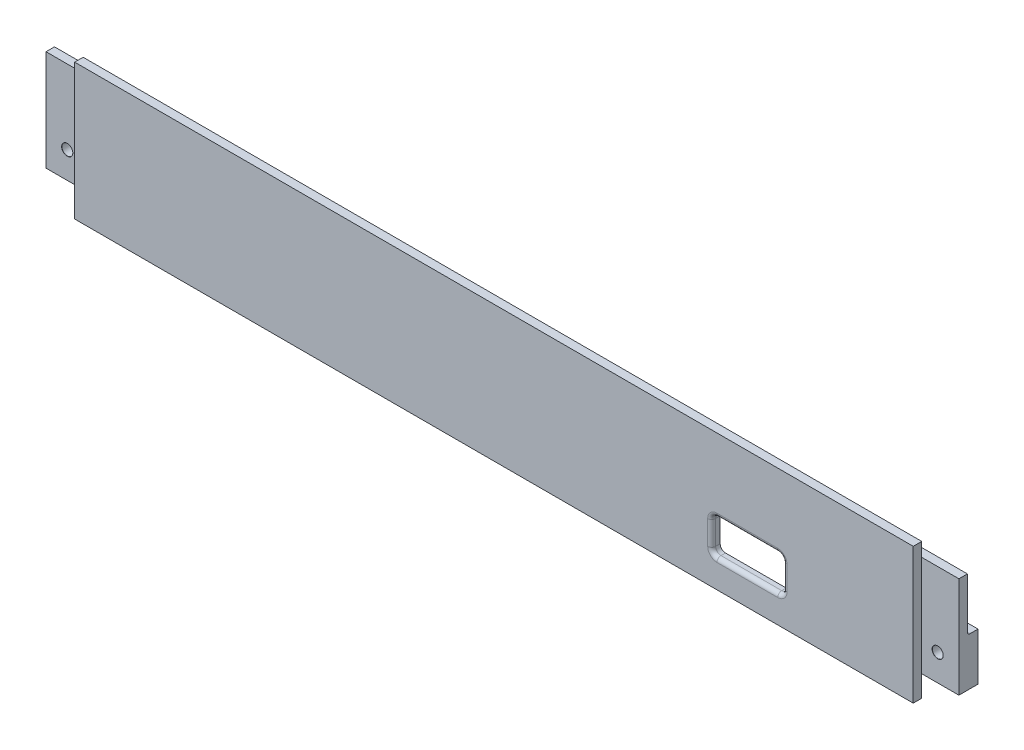
SolidWorks part; units mm, degrees
ref_plane "Front Plane" through (0, 0, 0) normal (0, 0, 1) x (1, 0, 0)
ref_plane "Top Plane" through (0, 0, 0) normal (0, 1, 0) x (1, 0, 0)
ref_plane "Right Plane" through (0, 0, 0) normal (1, 0, 0) x (0, 0, -1)
sketch "Sketch1" plane through (0, 0, 0) normal (0, 0, 1) x (1, 0, 0)
  line L0 (0, -55) -> (0, 55) construction
  line L1 (-79, 25.6) -> (79, 25.6)
  line L2 (-79, 25.6) -> (-79, 0)
  line L3 (-79, 0) -> (79, 0)
  line L4 (79, 25.6) -> (79, 0)
  line L5 (55, 0) -> (-55, 0) construction
  dimension "D1" = 158
  dimension "D2" = 25.6
  dimension "D3" = 79
  dimension "D4" = 0
extrude "Primary backplate" add sketch "Sketch1" along normal blind 1.6
sketch "Sketch2" plane through (0, 0, 0) normal (0, 0, 1) x (1, 0, 0)
  line L0 (-79, 0) -> (79, 0) construction
  line L1 (-86, 23) -> (86, 23)
  line L2 (-86, 23) -> (-86, 4)
  line L3 (-86, 4) -> (86, 4)
  line L4 (86, 23) -> (86, 4)
  line L5 (0, 26.3642) -> (0, -16.9121) construction
  line L6 (-79, 25.6) -> (-79, 0) construction
  dimension "D1" = 172
  dimension "D2" = 19
  dimension "D3" = 4
  dimension "D4" = 79
  dimension "D5" = 86
extrude "Plate thickener" add sketch "Sketch2" against normal blind 1.6
sketch "Sketch13" plane through (0, 0, -1.6) normal (0, 0, -1) x (-1, 0, 0)
  line L0 (86, 23) -> (86, 4) construction
  line L1 (-86, 4) -> (-77, 4)
  line L2 (-86, 4) -> (-86, 13)
  line L3 (-86, 13) -> (-77, 13)
  line L4 (-77, 4) -> (-77, 13)
  line L5 (86, 4) -> (77, 4)
  line L6 (86, 4) -> (86, 13)
  line L7 (86, 13) -> (77, 13)
  line L8 (77, 4) -> (77, 13)
  line L9 (86, 4) -> (-86, 4) construction
  dimension "D3" = 9
  dimension "D4" = 9
  dimension "D1" = 9
  dimension "D2" = 9
  dimension "D5" = 0
extrude "Thicker rear bolt blocks" add sketch "Sketch13" along normal blind 2
hole_wizard "Tap Drill for M2.5x0.45 Tap3" positions "3DSketch3" profile "Sketch5" hole size "M2.5x0.45" standard "ANSI Metric" end condition through all
sketch3d "3DSketch3"
  point P0 (-82, 9, 0)
  point P3 (82, 9, 0)
  dimension "D1" = 82
  dimension "D2" = 82
  dimension "D3" = 9
  dimension "D4" = 9
sketch "Sketch5" plane through (-82, 9, 0) normal (1, 0, 0) x (0, -1, 0)
  line L0 (0, 0) -> (0, 3.6)
  line L1 (0, 3.6) -> (1.025, 3.6)
  line L2 (1.025, 3.6) -> (1.025, 0.025)
  line L3 (1.025, 0.025) -> (1.05, 0)
  line L5 (1.05, 0) -> (0, 0)
  line L6 (-1.025, 0.025) -> (-1.05, 0) construction
  line L11 (0, -6.35) -> (0, 107.95) construction
  dimension "Thru Hole Dia." = 2.05
  dimension "Thru Hole Depth" = 3.6
  dimension "Near C'Sink Dia." = 2.1
  dimension "Near C'Sink Angle" = 90
ref_plane "PCB top" through (0, 1.6, 0) normal (0, 1, 0) x (1, 0, 0)
sketch "Sketch7" plane through (0, 1.6, 0) normal (0, 1, 0) x (1, 0, 0)
  line L0 (0, -1.76) -> (0, 1.76) construction
  line L1 (-80.9, 68.51) -> (80.9, 68.51) construction
  line L2 (-80.9, 68.51) -> (-80.9, 0.51) construction
  line L3 (-80.9, 0.51) -> (80.9, 0.51) construction
  line L4 (80.9, 68.51) -> (80.9, 0.51) construction
  line L5 (-14.08, 0) -> (14.08, 0) construction
  line L6 (-60.9, 68.51) -> (-60.9, 0) construction
  line L7 (70.9, 68.51) -> (70.9, 0) construction
  line L9 (-60.9, 0) -> (-52.9, 0)
  line L10 (-60.9, 0) -> (-60.9, 7)
  line L11 (-60.9, 7) -> (-52.9, 7)
  line L12 (-52.9, 0) -> (-52.9, 7)
  line L13 (70.9, 0) -> (62.9, 0)
  line L14 (70.9, 0) -> (70.9, 7)
  line L15 (70.9, 7) -> (62.9, 7)
  line L16 (62.9, 0) -> (62.9, 7)
  circle A0 centre (-56.9, 4.51) radius 1.3
  circle A1 centre (66.9, 4.51) radius 1.3
  dimension "D14" = 2.6
  dimension "D15" = 2.6
  dimension "D1" = 80.9
  dimension "D2" = 80.9
  dimension "D3" = 0.51
  dimension "D4" = 68
  dimension "D5" = 20
  dimension "D6" = 10
  dimension "8" = 8
  dimension "D8" = 7
  dimension "D9" = 8
  dimension "D10" = 7
  dimension "D11" = 4
  dimension "D7" = 4
  dimension "D12" = 4
  dimension "D13" = 4
extrude "Mounting bosses" add sketch "Sketch7" along normal blind 4 separate body
sketch "Sketch8" plane through (0, 0, 0) normal (0, 0, 1) x (1, 0, 0)
  line L1 (54.4613, 11.771) -> (41.0239, 11.771)
  line L2 (54.4613, 11.771) -> (54.4613, 5.2243)
  line L3 (54.4613, 5.2243) -> (41.0239, 5.2243)
  line L4 (41.0239, 11.771) -> (41.0239, 5.2243)
extrude "USB hole" cut sketch "Sketch8" against normal through all both and the other way through all
combine bodies "Combine1" operation type add bodies to combine 108 107 106
fillet "Fillet1" radius 0.5 10 edges at (-52.9, 4.8, -1.6) (-60.9, 4.8, -1.6) (-56.9, 5.6, -1.6) (70.9, 4.8, -1.6) (62.9, 4.8, -1.6) (66.9, 5.6, -1.6) (-77, 8.5, -1.6) (-81.5, 13, -1.6) (77, 8.5, -1.6) (81.5, 13, -1.6)
sketch "Sketch9" plane through (0, 0, -1.6) normal (0, 0, -1) x (-1, 0, 0)
  line L1 (-61.6916, 16.2443) -> (-32.4345, 16.2443)
  line L2 (-61.6916, 16.2443) -> (-61.6916, 0.4655)
  line L3 (-61.6916, 0.4655) -> (-32.4345, 0.4655)
  line L4 (-32.4345, 16.2443) -> (-32.4345, 0.4655)
extrude "module relief" cut sketch "Sketch9" against normal up to surface (1.6 mm away) up to face at (0, 24.3, 0)
fillet "Fillet2" radius 1 4 edges at (41.0239, 5.2243, 0.8) (54.4613, 5.2243, 0.8) (54.4613, 11.771, 0.8) (41.0239, 11.771, 0.8)
fillet "Fillet3" radius 0.75 8 edges at (41.3168, 11.4781, 1.6) (47.7426, 11.771, 1.6) (54.1684, 11.4781, 1.6) (54.4613, 8.4977, 1.6) (54.1684, 5.5172, 1.6) (47.7426, 5.2243, 1.6) (41.3168, 5.5172, 1.6) (41.0239, 8.4977, 1.6)
sketch "Sketch12" plane through (0, 0, -1.6) normal (0, 0, -1) x (-1, 0, 0)
  line L1 (-24.2469, 3.8271) -> (-20.6338, 3.8271)
  line L2 (-24.2469, 3.8271) -> (-24.2469, 1.9254)
  line L3 (-24.2469, 1.9254) -> (-20.6338, 1.9254)
  line L4 (-20.6338, 3.8271) -> (-20.6338, 1.9254)
extrude "LED hole" cut sketch "Sketch12" against normal offset from surface (3 mm away) 0.2 up to face at (47.7426, 8.4977, 1.6)
equation "\"D4@Sketch2\"=158/2"
equation "\"D5@Sketch2\"=172/2"
equation "\"D3@Sketch1\"=158/2"
equation "\"D1\"= 164 / 2"
equation "\"D1@3DSketch3\"=164/2"
equation "\"D2@3DSketch3\"=164/2"
equation "\"D1@Sketch7\"=161.8/2"
equation "\"D2@Sketch7\"=\"D1@Sketch7\""
equation "\"D9@Sketch7\"=\"8@Sketch7\""
equation "\"D10@Sketch7\"=\"D8@Sketch7\""
equation "\"D7@Sketch7\"=\"D11@Sketch7\""
equation "\"D15@Sketch7\"=\"D14@Sketch7\""
equation "\"D13@Sketch7\"=\"D12@Sketch7\""
equation "\"D3@Sketch13\"=\"D1@Sketch13\""
equation "\"D4@Sketch13\"=\"D2@Sketch13\""
